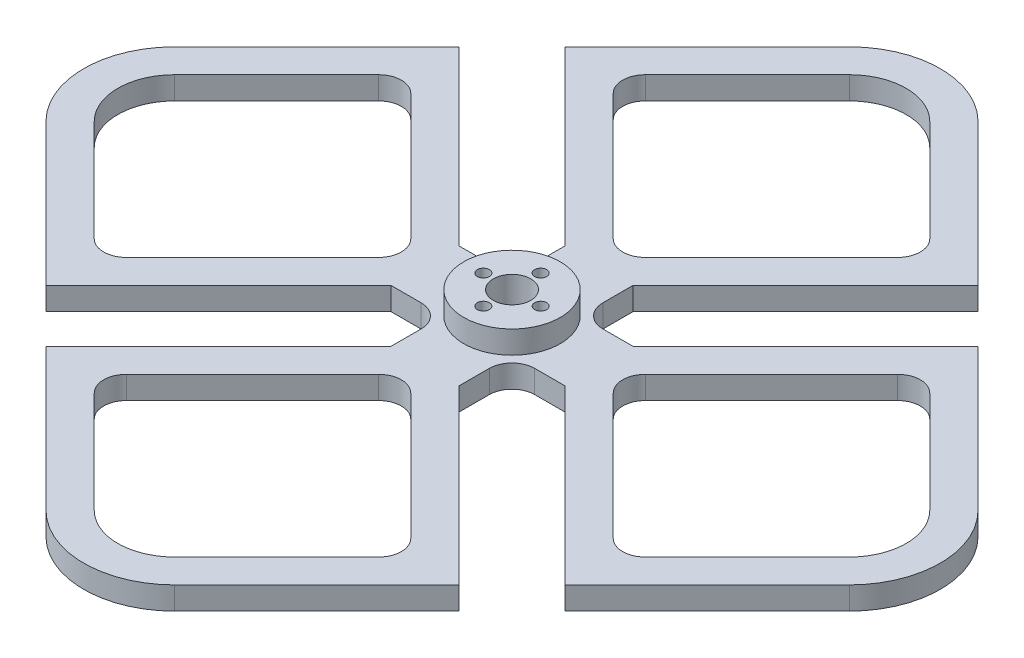
SolidWorks part; units mm, degrees
ref_plane "Front Plane" through (0, 0, 0) normal (0, 0, 1) x (1, 0, 0)
ref_plane "Top Plane" through (0, 0, 0) normal (0, 1, 0) x (1, 0, 0)
ref_plane "Right Plane" through (0, 0, 0) normal (1, 0, 0) x (0, 0, -1)
sketch "Sketch4" plane through (0, 0, 0) normal (0, 1, 0) x (1, 0, 0)
  line L8 (14.7955, 0) -> (72.4487, -57.6532)
  line L9 (14.7955, 0) -> (72.4487, 57.6532)
  line L10 (72.4487, -57.6532) -> (130.102, 0)
  line L11 (72.4487, 57.6532) -> (130.102, 0)
  line L13 (0, 9.525) -> (24.3205, 9.525)
  line L14 (0, 9.525) -> (0, -9.525)
  line L15 (0, -9.525) -> (24.3205, -9.525)
  line L16 (24.3205, 9.525) -> (24.3205, -9.525)
  dimension "D1" = 81.534
  dimension "D2" = 14.7955
  dimension "D3" = 19.05
extrude "Boss-Extrude5" add sketch "Sketch4" along normal blind 6.35 contours L9 L16 L8 L10 L11 | L16 L9 L8 | L14 L15 L8 L9 L13 region at (21.1455, 0, 0) region at (9.9723, 0, 0) region at (73.1586, 0, 0)
sketch "Sketch6" plane through (0, 0, 0) normal (0, 0, 1) x (1, 0, 0)
  line L0 (0, 0) -> (0, 27.64) construction
fillet "Fillet1" radius 25.4 1 edges at (130.102, 3.175, 0)
sketch "Sketch12" plane through (0, 6.35, 0) normal (0, 1, 0) x (1, 0, 0)
  line L14 (72.4487, -44.1829) -> (105.4063, -11.2253)
  line L15 (105.4063, 11.2253) -> (72.4487, 44.1829)
  line L16 (72.4487, 44.1829) -> (28.2659, 0)
  line L20 (28.2659, 0) -> (72.4487, -44.1829)
  line L21 (72.4487, -44.1829) -> (105.4063, -11.2253)
  line L22 (105.4063, 11.2253) -> (72.4487, 44.1829)
  line L23 (72.4487, 44.1829) -> (28.2659, 0)
  line L27 (28.2659, 0) -> (72.4487, -44.1829)
  arc A2 (105.4063, -11.2253) -> (105.4063, 11.2253) centre (94.181, 0) ccw
  arc A3 (105.4063, -11.2253) -> (105.4063, 11.2253) centre (94.181, 0) ccw
  dimension "D1" = 9.525
extrude "Cut-Extrude3" cut sketch "Sketch12" against normal through all
pattern_circular "CirPattern7" count 4 over 360 about axis through (0, 0, 0) along (0, 1, 0) of "Boss-Extrude5", "Fillet1", "Cut-Extrude3"
sketch "Sketch13" plane through (0, 6.35, 0) normal (0, 1, 0) x (1, 0, 0)
  circle A0 centre (0, 0) radius 13.4704
extrude "Boss-Extrude8" add sketch "Sketch13" along normal blind 6.35
sketch "Sketch1" plane through (0, 0, 0) normal (0, 1, 0) x (1, 0, 0)
  circle A0 centre (0, 0) radius 2.6905 construction
  circle A1 centre (0, 0) radius 5.227
  circle A2 centre (8, 0) radius 1.6865
  circle A6 centre (0, -8) radius 1.6865
  circle A7 centre (-8, 0) radius 1.6865
  circle A8 centre (0, 8) radius 1.6865
  point P15 (0, 0)
  dimension "D1" = 10.454
  dimension "D3" = 3.373
  dimension "D2" = 8
extrude "Cut-Extrude1" cut sketch "Sketch1" along normal through all
fillet "Fillet2" radius 6.35 16 edges at (-72.4487, 3.175, 44.1829) (-72.4487, 3.175, -44.1829) (-28.2659, 3.175, 0) (-44.1829, 3.175, -72.4487) (44.1829, 3.175, -72.4487) (0, 3.175, -28.2659) (72.4487, 3.175, -44.1829) (72.4487, 3.175, 44.1829) (28.2659, 3.175, 0) (44.1829, 3.175, 72.4487) (-44.1829, 3.175, 72.4487) (0, 3.175, 28.2659) (9.525, 3.175, -9.525) (-9.525, 3.175, -9.525) (-9.525, 3.175, 9.525) (9.525, 3.175, 9.525)
equation "\"tightTol\"= 0.005in"
equation "\"normTol\"= 0.01in"
equation "\"looseTol\"= 0.02in"
equation "\"D1@Sketch1\"=\"normTol\"+10.2mm"
equation "\"D2@Sketch1\"=8mm"
equation "\"D1@Sketch4\"=3.25-2*\"looseTol\""
equation "\"D2@Sketch4\"=9/16+\"looseTol\""
equation "\"D3@Sketch1\"=3.5mm-\"tightTol\""
